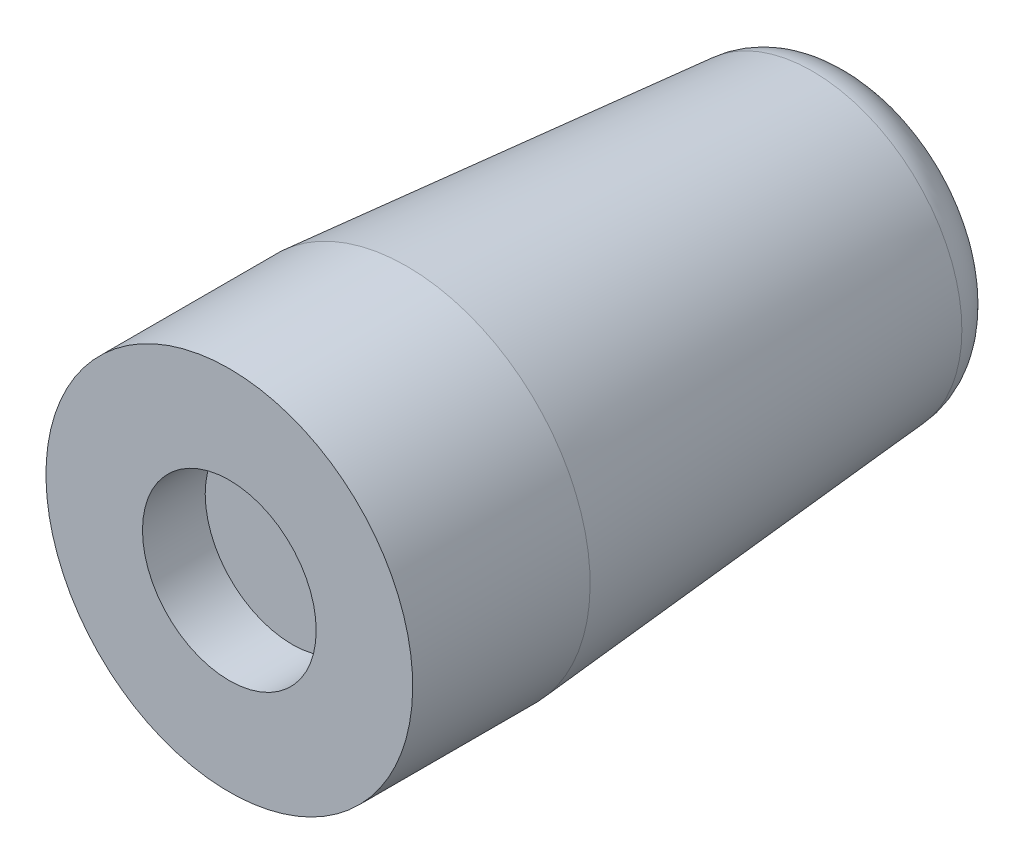
SolidWorks part; units mm, degrees
ref_plane "前视基准面" through (0, 0, 0) normal (0, 0, 1) x (1, 0, 0)
ref_plane "上视基准面" through (0, 0, 0) normal (0, 1, 0) x (1, 0, 0)
ref_plane "右视基准面" through (0, 0, 0) normal (1, 0, 0) x (0, 0, -1)
sketch "草图1" plane through (0, 0, 0) normal (1, 0, 0) x (0, 0, -1)
  line L0 (6.1867, 3.0206) -> (6.1867, 0)
  line L1 (6.3523, 0) -> (-6.6477, 0) construction
  line L2 (-6.8133, 0) -> (-6.8133, 3.8)
  line L3 (-6.8133, 3.8) -> (-3.1364, 3.8)
  line L4 (-3.1364, 3.8) -> (6.1867, 3.0206)
  line L5 (6.1867, 0) -> (-6.8133, 0)
  dimension "D1" = 3.8
  dimension "D2" = 13
revolve "旋转1" add sketch "草图1" angle 360 about L1
sketch "草图5" plane through (0, 0, 6.8133) normal (0, 0, 1) x (1, 0, 0)
  circle A0 centre (0, 0) radius 1.8
  dimension "D1" = 3.6
extrude "切除-拉伸2" cut sketch "草图5" against normal blind 1.3
fillet "圆角1" radius 1 1 edges at (0, 3.0206, -6.1867)
sketch "草图6" plane through (0, 0, -6.1867) normal (0, 0, -1) x (-1, 0, 0)
  circle A0 centre (0, 0) radius 1.694
extrude "切除-拉伸3" cut sketch "草图6" against normal blind 0.5
fillet "圆角2" radius 1 1 edges at (0, 1.694, -5.6867)
